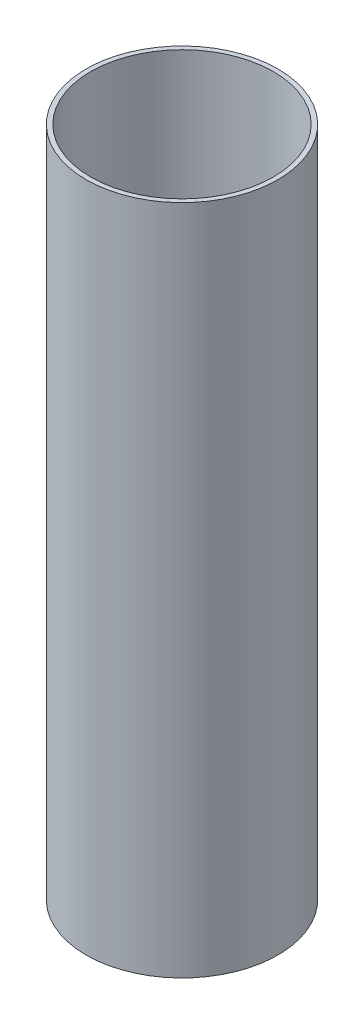
SolidWorks part; units mm, degrees
ref_plane "Front Plane" through (0, 0, 0) normal (0, 0, 1) x (1, 0, 0)
ref_plane "Top Plane" through (0, 0, 0) normal (0, 1, 0) x (1, 0, 0)
ref_plane "Right Plane" through (0, 0, 0) normal (1, 0, 0) x (0, 0, -1)
sketch "Sketch3" plane through (0, 0, 0) normal (0, 1, 0) x (1, 0, 0)
  circle A0 centre (0, 0) radius 21
  dimension "D1" = 42
extrude "Boss-Extrude2" add sketch "Sketch3" along normal blind 2 from surface starting at plane "Top Plane"
sketch "Sketch4" plane through (0, 2, 0) normal (0, 1, 0) x (1, 0, 0)
  circle A1 centre (0, 0) radius 10.05
  dimension "D1" = 20.1
extrude "Cut-Extrude2" cut sketch "Sketch4" against normal blind 12.5
sketch "Sketch5" plane through (0, 2, 0) normal (0, 1, 0) x (1, 0, 0)
  circle A0 centre (0, 0) radius 21
  dimension "D1" = 42
extrude "Boss-Extrude3" add sketch "Sketch5" along normal blind 24
sketch "Sketch6" plane through (0, 26, 0) normal (0, 1, 0) x (1, 0, 0)
  circle A0 centre (0, 0) radius 20
  dimension "D1" = 40
extrude "Cut-Extrude3" cut sketch "Sketch6" against normal blind 24
sketch "Sketch7" plane through (0, 26, 0) normal (0, 1, 0) x (1, 0, 0)
  circle A0 centre (0, 0) radius 21
  dimension "D1" = 42
extrude "Boss-Extrude4" add sketch "Sketch7" along normal blind 12.5
sketch "Sketch8" plane through (0, 38.5, 0) normal (0, 1, 0) x (1, 0, 0)
  circle A0 centre (0, 0) radius 10.05
  dimension "D1" = 20.1
extrude "Cut-Extrude4" cut sketch "Sketch8" against normal blind 12.5
sketch "Sketch9" plane through (0, 38.5, 0) normal (0, 1, 0) x (1, 0, 0)
  circle A0 centre (0, 0) radius 21
  dimension "D1" = 42
extrude "Boss-Extrude5" add sketch "Sketch9" along normal blind 19
sketch "Sketch10" plane through (0, 57.5, 0) normal (0, 1, 0) x (1, 0, 0)
  circle A0 centre (0, 0) radius 20
  dimension "D1" = 40
extrude "Cut-Extrude5" cut sketch "Sketch10" against normal blind 19
sketch "Sketch11" plane through (0, 57.5, 0) normal (0, 1, 0) x (1, 0, 0)
  circle A0 centre (0, 0) radius 21
  dimension "D1" = 42
extrude "Boss-Extrude6" add sketch "Sketch11" along normal blind 14.5
sketch "Sketch12" plane through (0, 72, 0) normal (0, 1, 0) x (1, 0, 0)
  circle A0 centre (0, 0) radius 7.5
  dimension "D1" = 15
extrude "Cut-Extrude6" cut sketch "Sketch12" against normal blind 14.5
sketch "Sketch13" plane through (0, 72, 0) normal (0, 1, 0) x (1, 0, 0)
  circle A0 centre (0, 0) radius 21
  dimension "D1" = 42
extrude "Boss-Extrude7" add sketch "Sketch13" along normal blind 75
sketch "Sketch14" plane through (0, 147, 0) normal (0, 1, 0) x (1, 0, 0)
  circle A0 centre (0, 0) radius 20
  dimension "D1" = 40
extrude "Cut-Extrude7" cut sketch "Sketch14" against normal blind 75
chamfer "Chamfer7" distance 11 angle 45 1 edges at (0, 26, 10.05)
chamfer "Chamfer8" distance 12.5 angle 45 1 edges at (0, 57.5, 7.5)
equation "\"holeDia\"= 42"
equation "\"D1@Sketch3\"=\"holeDia\""
equation "\"D1@Sketch5\"=\"holeDia\""
equation "\"D1@Sketch7\"=\"holeDia\""
equation "\"D1@Sketch9\"=\"holeDia\""
equation "\"D1@Sketch11\"=\"holeDia\""
equation "\"D1@Sketch13\"=\"holeDia\""
equation "\"innerDiam\"= 40"
equation "\"centerRingDiam\"=20.1"
equation "\"D1@Sketch4\"=\"centerRingDiam\""
equation "\"D1@Sketch6\"=\"innerDiam\""
equation "\"D1@Sketch8\"=\"centerRingDiam\""
equation "\"D1@Sketch10\"=\"innerDiam\""
equation "\"D1@Sketch14\"=\"innerDiam\""
